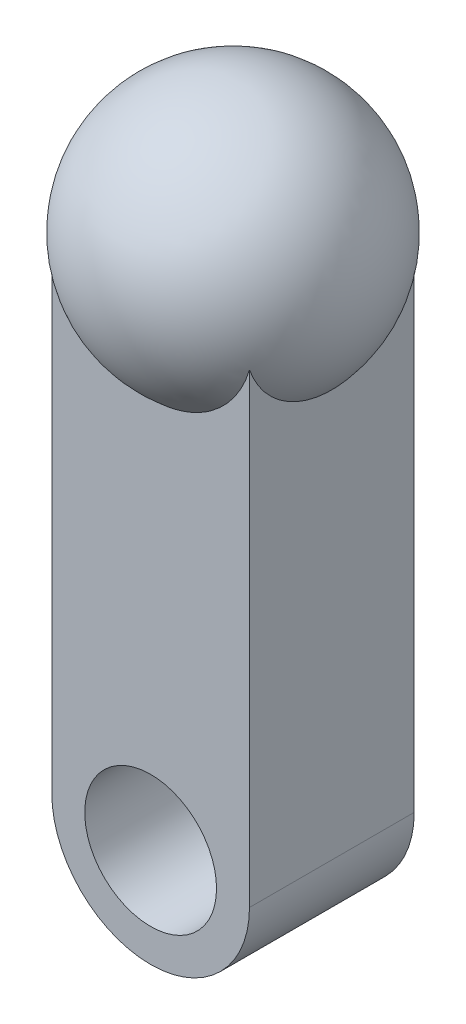
SolidWorks part; units mm, degrees
ref_plane "Alzado" through (0, 0, 0) normal (0, 0, 1) x (1, 0, 0)
ref_plane "Planta" through (0, 0, 0) normal (0, 1, 0) x (1, 0, 0)
ref_plane "Vista lateral" through (0, 0, 0) normal (1, 0, 0) x (0, 0, -1)
sketch "Croquis1" plane through (0, 0, 0) normal (0, 0, 1) x (1, 0, 0)
  line L0 (0, 0) -> (0, 15) construction
  line L1 (3, 15) -> (3, 0)
  line L2 (-3, 15) -> (-3, 0)
  circle A0 centre (0, 0) radius 2
  arc A1 (-3, 0) -> (3, 0) centre (0, 0) ccw
  circle A2 centre (0, 15) radius 2
  arc A3 (3, 15) -> (-3, 15) centre (0, 15) ccw
extrude "Saliente-Extruir1" add sketch "Croquis1" along normal blind 2.5 and the other way blind 2.5
sketch "Croquis2" plane through (0, 0, 0) normal (0, 0, 1) x (1, 0, 0)
  line L1 (0, 11) -> (0, 19)
  arc A0 (0, 11) -> (0, 19) centre (0, 15) ccw
revolve "Revolución1" add sketch "Croquis2" angle 360 about L1
